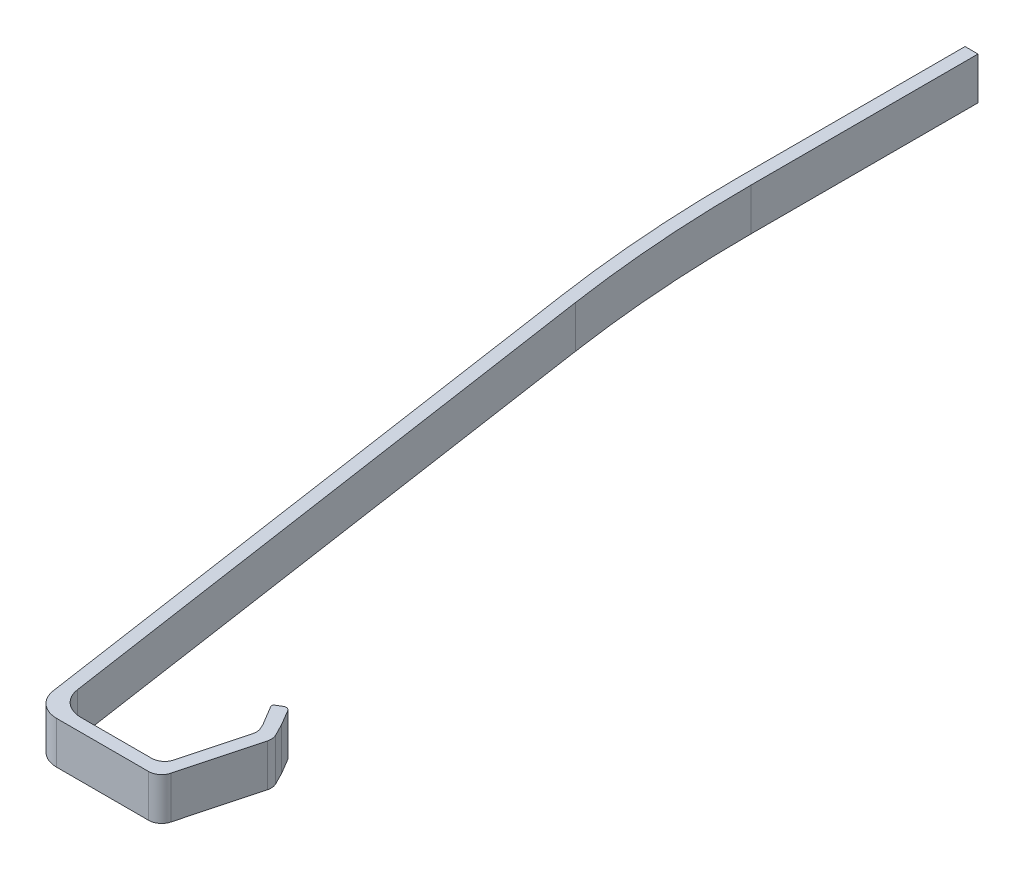
SolidWorks part; units mm, degrees
ref_plane "Front Plane" through (0, 0, 0) normal (0, 0, 1) x (1, 0, 0)
ref_plane "Top Plane" through (0, 0, 0) normal (0, 1, 0) x (1, 0, 0)
ref_plane "Right Plane" through (0, 0, 0) normal (1, 0, 0) x (0, 0, -1)
sketch "Sketch1" plane through (0, 0, 0) normal (0, 1, 0) x (1, 0, 0)
  line L0 (14.1397, -55) -> (14.1397, -107.573)
  line L1 (17.3608, -151.4166) -> (37.3725, -286.8769)
  line L2 (66.4728, -275.3649) -> (62.63, -289.7731)
  line L3 (65.4207, -271.6456) -> (63.1055, -267.7869)
  line L4 (63.277, -267.1009) -> (64.5572, -266.3328)
  line L5 (66.3119, -273.365) -> (65.9707, -272.6035)
  line L6 (65.8054, -272.2868) -> (65.4207, -271.6456)
  line L8 (43.3081, -292) -> (59.7313, -292)
  line L9 (-48.6621, -292) -> (48.6621, -292) construction
  line L10 (11.1397, -55) -> (11.1397, -107.573)
  line L11 (14.393, -151.855) -> (34.7831, -289.8769)
  line L12 (40.7187, -295) -> (62.036, -295)
  line L13 (69.6458, -275.1095) -> (64.9347, -292.7731)
  line L14 (67.9985, -270.1803) -> (69.4209, -272.9759)
  line L15 (68.9304, -271.8722) -> (68.9304, -271.8722)
  line L16 (68.9304, -271.8722) -> (69.0222, -271.8171)
  line L17 (67.9985, -270.1803) -> (65.9328, -266.6819)
  line L18 (11.1397, -129.8335) -> (35.54, -295) construction
  line L19 (35.54, -295) -> (64.3408, -295) construction
  line L20 (38.1294, -292) -> (62.036, -292) construction
  line L21 (14.1397, -129.6131) -> (38.1294, -292) construction
  line L22 (66.7472, -274.3364) -> (62.036, -292) construction
  line L23 (69.9201, -274.081) -> (64.3408, -295) construction
  line L24 (69.9201, -274.081) -> (68.9304, -271.8722) construction
  line L25 (66.7472, -274.3364) -> (65.8975, -272.4403) construction
  line L26 (65.8975, -272.4403) -> (64.9062, -270.7881) construction
  line L27 (64.9062, -270.7881) -> (67.4787, -269.2447) construction
  line L28 (14.1397, -55) -> (14.1397, -129.6131) construction
  line L29 (11.1397, -55) -> (11.1397, -129.8335) construction
  line L30 (11.1397, -55) -> (14.1397, -55)
  arc A0 (34.7831, -289.8769) -> (40.7187, -295) centre (40.7187, -289) ccw
  arc A1 (43.3081, -292) -> (37.3725, -286.8769) centre (43.3081, -286) cw
  arc A2 (59.7313, -292) -> (62.63, -289.7731) centre (59.7313, -289) ccw
  arc A3 (62.036, -295) -> (64.9347, -292.7731) centre (62.036, -292) ccw
  arc A4 (69.6458, -275.1095) -> (69.4209, -272.9759) centre (66.7472, -274.3364) ccw
  arc A5 (65.9707, -272.6035) -> (65.8054, -272.2868) centre (63.233, -273.8303) ccw
  arc A6 (66.4728, -275.3649) -> (66.3119, -273.365) centre (63.5742, -274.5918) ccw
  arc A7 (67.9347, -270.0723) -> (67.9985, -270.1803) centre (67.1072, -270.6337) cw
  arc A9 (14.1397, -107.573) -> (17.3608, -151.4166) centre (314.1397, -107.573) ccw
  arc A10 (11.1397, -107.573) -> (14.393, -151.855) centre (314.1397, -107.573) ccw
  arc A11 (65.9328, -266.6819) -> (64.5572, -266.3328) centre (65.0717, -267.1903) ccw
  arc A12 (63.1055, -267.7869) -> (63.277, -267.1009) centre (63.5342, -267.5297) cw
  point P27 (38.1294, -292)
  dimension "D2" = 6
  dimension "D3" = 3
  dimension "D4" = 3
  dimension "D5" = 1
  dimension "D6" = 300
  dimension "D7" = 303
  dimension "D8" = 1
  dimension "D9" = 0.5
  dimension "D1" = 3
extrude "Boss-Extrude1" add sketch "Sketch1" along normal blind 4.9 and the other way blind 4.9 contours L10 A10 L11 A0 L12 A3 L13 A4 L14 A7 A11 L6 A5 L5 A6 L2 A2 L8 A1 L1 A9 L0 L30 region at (11.6692, 0, 81.2865)
